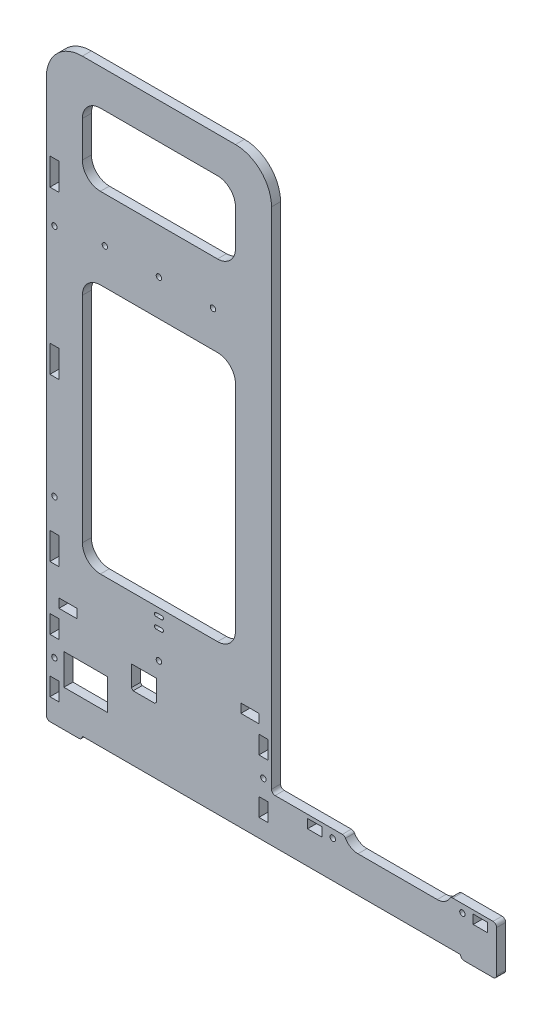
SolidWorks part; units mm, degrees
material "Maple"
ref_plane "Front Plane" through (0, 0, 0) normal (0, 0, 1) x (1, 0, 0)
ref_plane "Top Plane" through (0, 0, 0) normal (0, 1, 0) x (1, 0, 0)
ref_plane "Right Plane" through (0, 0, 0) normal (1, 0, 0) x (0, 0, -1)
sketch "Sketch1" plane through (0, 0, 0) normal (0, 0, 1) x (1, 0, 0)
  line L0 (0, 0) -> (0, 64)
  line L1 (0, 64) -> (125, 64)
  line L2 (125, 64) -> (125, 27)
  line L3 (125, 27) -> (250, 27)
  line L4 (250, 27) -> (250, 0)
  line L5 (250, 0) -> (0, 0)
  dimension "D1" = 64
  dimension "D2" = 125
  dimension "D3" = 125
  dimension "D4" = 27
extrude "Boss-Extrude1" add sketch "Sketch1" along normal blind 5
sketch "Sketch7" plane through (0, 0, 5) normal (0, 0, 1) x (1, 0, 0)
  line L0 (48.2, 38.94) -> (60.2, 38.94) construction
  line L1 (48.2, 38.94) -> (48.2, 49.44) construction
  line L2 (48.2, 49.44) -> (60.2, 49.44) construction
  line L3 (60.2, 38.94) -> (60.2, 49.44) construction
  line L4 (47.2, 37.94) -> (61.2, 37.94)
  line L5 (61.2, 37.94) -> (61.2, 50.44)
  line L6 (47.2, 50.44) -> (61.2, 50.44)
  line L7 (47.2, 37.94) -> (47.2, 50.44)
  line L8 (10.74, 28.1) -> (10.74, 21.4) construction
  line L9 (10.74, 36.6) -> (33.06, 36.6) construction
  line L10 (10.74, 36.6) -> (10.74, 28.1) construction
  line L11 (10.74, 28.1) -> (33.06, 28.1) construction
  line L12 (33.06, 36.6) -> (33.06, 28.1) construction
  line L13 (10.74, 21.4) -> (33.06, 21.4) construction
  line L14 (33.06, 21.4) -> (33.06, 28.1) construction
  line L15 (9.74, 28.1) -> (9.74, 20.4)
  line L16 (9.74, 20.4) -> (34.06, 20.4)
  line L17 (34.06, 20.4) -> (34.06, 28.1)
  line L18 (34.06, 37.6) -> (34.06, 28.1)
  line L19 (9.74, 37.6) -> (34.06, 37.6)
  line L20 (9.74, 37.6) -> (9.74, 28.1)
  line L21 (0, 64) -> (0, 0) construction
  line L25 (0, 0) -> (250, 0) construction
  dimension "D1" = 10.5
  dimension "D2" = 12
  dimension "D3" = 15.14
  dimension "D4" = 10.84
  dimension "D5" = 22.32
  dimension "D6" = 8.5
  dimension "D7" = 15.2
  dimension "D9" = 10.74
  dimension "D10" = 36.6
  dimension "D8" = 1
extrude "Cut-Extrude4" cut sketch "Sketch7" against normal through all
sketch "Sketch3" plane through (0, 0, 5) normal (0, 0, 1) x (1, 0, 0)
  line L1 (0, 64) -> (125, 64)
  line L2 (0, 64) -> (0, 329)
  line L3 (0, 329) -> (125, 329)
  line L4 (125, 64) -> (125, 329)
  dimension "D1" = 265
extrude "Boss-Extrude2" add sketch "Sketch3" against normal up to surface (5 mm away) up to face at (21.9, 29, 0)
sketch "Sketch4" plane through (0, 0, 5) normal (0, 0, 1) x (1, 0, 0)
  line L0 (62.5, 309) -> (62.5, 329) construction
  line L1 (20, 309) -> (105, 309)
  line L2 (20, 309) -> (20, 269)
  line L3 (20, 269) -> (105, 269)
  line L4 (105, 309) -> (105, 269)
  line L5 (125, 329) -> (0, 329) construction
  line L6 (105, 289) -> (125, 289) construction
  line L7 (125, 27) -> (125, 329) construction
  line L8 (0, 0) -> (250, 0) construction
  line L9 (105, 224) -> (20, 224)
  line L10 (105, 224) -> (105, 85)
  line L11 (105, 85) -> (20, 85)
  line L12 (20, 224) -> (20, 85)
  dimension "D1" = 20
  dimension "D2" = 20
  dimension "D3" = 40
  dimension "D4" = 85
  dimension "D5" = 45
extrude "Cut-Extrude2" cut sketch "Sketch4" against normal through all
sketch "Sketch2" plane through (0, 0, 5) normal (0, 0, 1) x (1, 0, 0)
  line L0 (0, 329) -> (0, 0) construction
  line L1 (7, 62) -> (17, 62)
  line L2 (7, 62) -> (7, 57)
  line L3 (7, 57) -> (17, 57)
  line L4 (17, 62) -> (17, 57)
  line L5 (108, 62) -> (118, 62)
  line L6 (108, 62) -> (108, 57)
  line L7 (108, 57) -> (118, 57)
  line L8 (118, 62) -> (118, 57)
  line L9 (4.5, 22) -> (4.5, 42) construction
  line L10 (125, 27) -> (125, 329) construction
  line L11 (250, 27) -> (125, 27) construction
  line L12 (245, 25) -> (237, 25)
  line L13 (245, 25) -> (245, 20)
  line L14 (245, 20) -> (237, 20)
  line L15 (237, 25) -> (237, 20)
  line L16 (145, 25) -> (153, 25)
  line L17 (145, 25) -> (145, 20)
  line L18 (145, 20) -> (153, 20)
  line L19 (153, 25) -> (153, 20)
  line L20 (250, 0) -> (250, 27) construction
  line L21 (173, 30) -> (217, 30) construction
  line L22 (153, 20) -> (237, 20) construction
  line L23 (62.5, 64) -> (62.5, 0) construction
  line L24 (123, 52) -> (118, 52)
  line L25 (123, 52) -> (123, 42)
  line L26 (123, 42) -> (118, 42)
  line L27 (118, 52) -> (118, 42)
  line L28 (123, 22) -> (118, 22)
  line L29 (123, 22) -> (123, 12)
  line L30 (123, 12) -> (118, 12)
  line L31 (118, 22) -> (118, 12)
  line L32 (7, 22) -> (7, 12)
  line L33 (2, 12) -> (7, 12)
  line L34 (2, 22) -> (2, 12)
  line L35 (2, 22) -> (7, 22)
  line L36 (7, 52) -> (7, 42)
  line L37 (2, 42) -> (7, 42)
  line L38 (2, 52) -> (2, 42)
  line L39 (2, 52) -> (7, 52)
  line L40 (0, 0) -> (250, 0) construction
  line L41 (173, 22) -> (217, 22)
  line L42 (173, 38) -> (217, 38)
  line L43 (0, 64) -> (125, 64) construction
  line L44 (20, 0) -> (230, 0)
  line L45 (20, 0) -> (20, 2)
  line L46 (20, 2) -> (230, 2)
  line L47 (230, 0) -> (230, 2)
  line L48 (0, 329) -> (0, 0) construction
  line L49 (125, 27) -> (125, 329) construction
  line L50 (17, 59.5) -> (62.5, 59.5) construction
  line L51 (2, 77) -> (7, 77)
  line L52 (2, 77) -> (2, 92)
  line L53 (2, 92) -> (7, 92)
  line L54 (7, 77) -> (7, 92)
  line L55 (2, 272) -> (7, 272)
  line L56 (2, 272) -> (2, 257)
  line L57 (2, 257) -> (7, 257)
  line L58 (7, 272) -> (7, 257)
  line L59 (2, 182) -> (7, 182)
  line L60 (2, 182) -> (2, 167)
  line L61 (2, 167) -> (7, 167)
  line L62 (7, 182) -> (7, 167)
  line L63 (153, 22.5) -> (159, 22.5) construction
  line L64 (195, 20) -> (195, 2) construction
  line L65 (61, 81) -> (64, 81) construction
  line L66 (61, 82) -> (64, 82)
  line L67 (61, 80) -> (64, 80)
  line L68 (61, 75) -> (64, 75) construction
  line L69 (61, 76) -> (64, 76)
  line L70 (61, 74) -> (64, 74)
  line L71 (20, 85) -> (105, 85) construction
  line L72 (4.5, 92) -> (4.5, 109.5) construction
  line L73 (4.5, 239.5) -> (4.5, 257) construction
  arc A0 (173, 38) -> (173, 22) centre (173, 30) ccw
  arc A1 (217, 22) -> (217, 38) centre (217, 30) ccw
  circle A2 centre (4.5, 32) radius 1.5
  circle A3 centre (62.5, 59.5) radius 1.5
  circle A4 centre (120.5, 32) radius 1.5
  circle A5 centre (159, 22.5) radius 1.5
  circle A6 centre (231, 22.5) radius 1.5
  arc A7 (61, 82) -> (61, 80) centre (61, 81) ccw
  arc A8 (64, 80) -> (64, 82) centre (64, 81) ccw
  arc A9 (61, 76) -> (61, 74) centre (61, 75) ccw
  arc A10 (64, 74) -> (64, 76) centre (64, 75) ccw
  circle A11 centre (4.5, 109.5) radius 1.5
  circle A12 centre (4.5, 239.5) radius 1.5
  point P29 (165, 30)
  point P38 (120.5, 52)
  point P55 (225, 30)
  point P93 (62.5, 81)
  point P98 (62.5, 75)
  point P105 (65, 81)
  point P106 (60, 81)
  point P113 (7, 264.5)
  point P114 (2, 84.5)
  dimension "D9" = 20
  dimension "D10" = 16
  dimension "D25" = 3
  dimension "D1" = 7
  dimension "D2" = 64
  dimension "D3" = 5
  dimension "D4" = 10
  dimension "D5" = 7
  dimension "D6" = 2
  dimension "D7" = 100
  dimension "D8" = 5
  dimension "D11" = 10
  dimension "D12" = 20
  dimension "D13" = 20
  dimension "D14" = 40
  dimension "D15" = 10
  dimension "D16" = 2
  dimension "D17" = 2
  dimension "D18" = 20
  dimension "D19" = 2
  dimension "D20" = 65
  dimension "D21" = 15
  dimension "D22" = 180
  dimension "D23" = 90
  dimension "D24" = 8
  dimension "D26" = 6
  dimension "D27" = 2
  dimension "D28" = 5
  dimension "D29" = 4
  dimension "D30" = 6
  dimension "D31" = 25
  dimension "D32" = 25
extrude "Cut-Extrude1" cut sketch "Sketch2" against normal through all
sketch "Sketch5" plane through (0, 0, 0) normal (0, 0, -1) x (-1, 0, 0)
  line L1 (-125, 329) -> (0, 329) construction
  line L2 (-62.5, 269) -> (-62.5, 244) construction
  line L3 (-20, 269) -> (-105, 269) construction
  circle A0 centre (-92.5, 244) radius 1.5
  circle A1 centre (-62.5, 244) radius 1.5
  circle A2 centre (-32.5, 244) radius 1.5
  dimension "D1" = 3
  dimension "D3" = 85
  dimension "D4" = 30
  dimension "D5" = 30
extrude "Cut-Extrude3" cut sketch "Sketch5" against normal through all
fillet "Fillet1" radius 2 8 edges at (250, 0, 2.5) (250, 27, 2.5) (0, 0, 2.5) (125, 27, 2.5) (224.4162, 27, 2.5) (165.5838, 27, 2.5) (230, 0, 2.5) (20, 0, 2.5)
fillet "Fillet2" radius 10 8 edges at (105, 309, 2.5) (105, 269, 2.5) (20, 269, 2.5) (20, 309, 2.5) (105, 85, 2.5) (20, 85, 2.5) (105, 224, 2.5) (20, 224, 2.5)
fillet "Fillet3" radius 20 2 edges at (125, 329, 2.5) (0, 329, 2.5)
chamfer "Chamfer1" distance 1 angle 45 2 edges at (61.2, 37.94, 2.5) (47.2, 37.94, 2.5)
